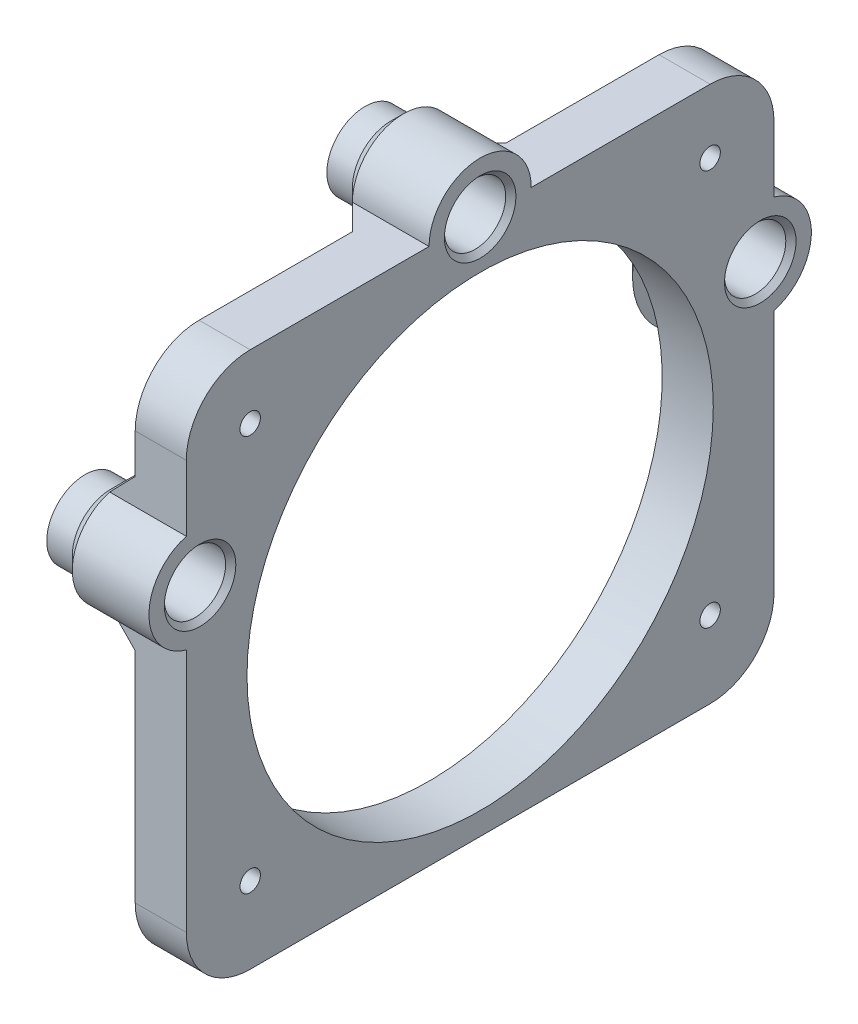
SolidWorks part; units mm, degrees
ref_plane "前视基准面" through (0, 0, 0) normal (0, 0, 1) x (1, 0, 0)
ref_plane "上视基准面" through (0, 0, 0) normal (0, 1, 0) x (1, 0, 0)
ref_plane "右视基准面" through (0, 0, 0) normal (1, 0, 0) x (0, 0, -1)
other "Configuration Table"
sketch "草图1" plane through (0, 0, 0) normal (1, 0, 0) x (0, 0, -1)
  line L1 (0, 0) -> (46, 0)
  line L2 (0, 0) -> (0, -41)
  line L3 (0, -41) -> (46, -41)
  line L4 (46, 0) -> (46, -41)
  circle A0 centre (5, -5) radius 0.8
  circle A1 centre (41, -5) radius 0.8
  circle A2 centre (5, -36) radius 0.8
  circle A3 centre (41, -36) radius 0.8
  dimension "D1" = 1.6
  dimension "D2" = 1.6
  dimension "D3" = 1.6
  dimension "D4" = 1.6
  dimension "D7" = 46
  dimension "D8" = 41
  dimension "D5" = 5
  dimension "D6" = 5
  dimension "D9" = 5
  dimension "D10" = 5
  dimension "D11" = 5
  dimension "D12" = 5
  dimension "D13" = 5
  dimension "D14" = 5
extrude "凸台-拉伸1" add sketch "草图1" along normal blind 4
sketch "草图2" plane through (0, 0, 0) normal (-1, 0, 0) x (0, 0, 1)
  line L1 (-46, 0) -> (0, 0) construction
  circle A0 centre (-44.925, -14) radius 4
  circle A1 centre (-1.075, -14) radius 4
  circle A2 centre (-23, 0) radius 4
  point P8 (-23, 0)
  dimension "D7" = 8
  dimension "D8" = 8
  dimension "D9" = 8
  dimension "D2" = 0
  dimension "D3" = 14
  dimension "D4" = 14
  dimension "D5" = 43.85
  dimension "D6" = 21.925
extrude "凸台-拉伸2" add sketch "草图2" against normal blind 4
sketch "草图3" plane through (0, 0, 0) normal (-1, 0, 0) x (0, 0, 1)
  circle A0 centre (-44.925, -14) radius 3
  circle A1 centre (-23, 0) radius 3
  circle A2 centre (-1.075, -14) radius 3
  dimension "D1" = 6
  dimension "D2" = 6
  dimension "D3" = 6
extrude "凸台-拉伸3" add sketch "草图3" along normal blind 5
sketch "草图4" plane through (-5, 0, 0) normal (-1, 0, 0) x (0, 0, 1)
  circle A0 centre (-44.925, -14) radius 1.6
  circle A1 centre (-23, 0) radius 1.6
  circle A2 centre (-1.075, -14) radius 1.6
  dimension "D1" = 3.2
  dimension "D2" = 3.2
  dimension "D3" = 3.2
extrude "切除-拉伸2" cut sketch "草图4" against normal through all
sketch "草图5" plane through (4, 0, 0) normal (1, 0, 0) x (0, 0, -1)
  circle A0 centre (1.075, -14) radius 2.4
  circle A1 centre (23, 0) radius 2.4
  circle A2 centre (44.925, -14) radius 2.4
  dimension "D1" = 4.8
  dimension "D2" = 4.8
  dimension "D3" = 4.8
extrude "切除-拉伸3" cut sketch "草图5" against normal blind 4.2
chamfer "倒角1" distance 0.4 angle 45 3 edges at (4, -14, -47.325) (4, 0, -25.4) (4, -14, -3.475)
chamfer "倒角2" distance 3 angle 45 3 edges at (0, -14, -4.075) (0, 0, -26) (0, -14, -47.925)
sketch "草图6" plane through (0, 0, 0) normal (-1, 0, 0) x (0, 0, 1)
  circle A0 centre (-23, -22) radius 18.25
  dimension "D1" = 36.5
extrude "切除-拉伸4" cut sketch "草图6" against normal blind 4
sketch "草图7" plane through (0, -41, 0) normal (0, -1, 0) x (-1, 0, 0)
  line L1 (0, 0) -> (-4, 0)
  line L2 (0, 0) -> (0, 46)
  line L3 (0, 46) -> (-4, 46)
  line L4 (-4, 0) -> (-4, 46)
extrude "凸台-拉伸4" add sketch "草图7" along normal blind 1
fillet "圆角2" radius 5 4 edges at (2, 0, 0) (2, 0, -46) (2, -42, -46) (2, -42, 0)
equation "\"D7@草图1\"=36+10"
equation "\"D8@草图1\"=31+10"
equation "\"D6@草图2\"=\"D5@草图2\"/2"
